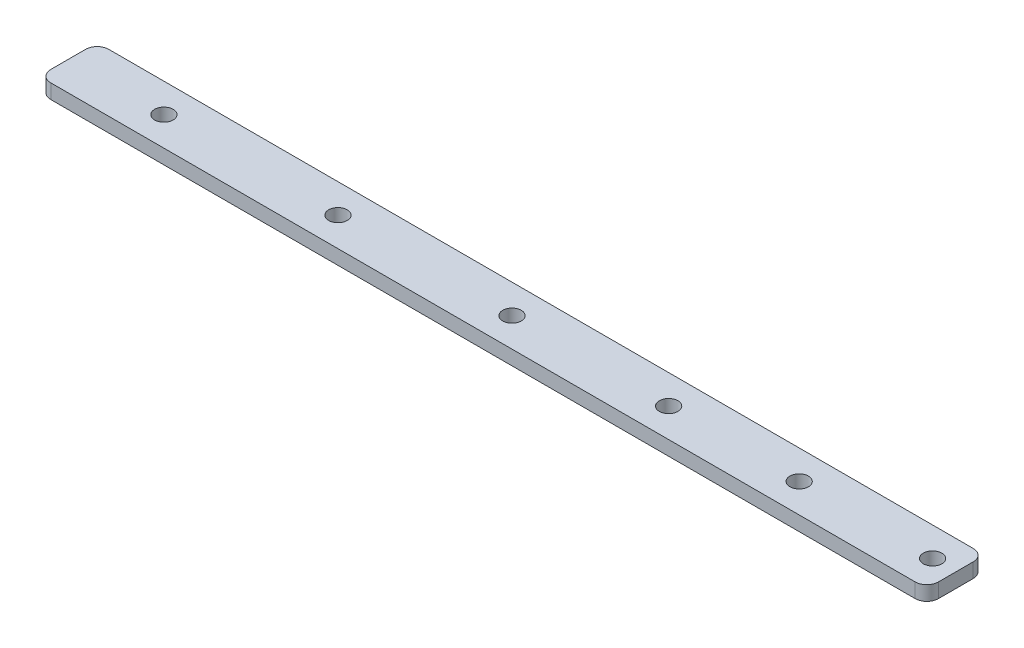
SolidWorks part; units mm, degrees
ref_plane "Front Plane" through (0, 0, 0) normal (0, 0, 1) x (1, 0, 0)
ref_plane "Top Plane" through (0, 0, 0) normal (0, 1, 0) x (1, 0, 0)
ref_plane "Right Plane" through (0, 0, 0) normal (1, 0, 0) x (0, 0, -1)
sketch "Sketch1" plane through (0, 0, 0) normal (0, 1, 0) x (1, 0, 0)
  line L1 (-97.155, -6.35) -> (97.155, -6.35)
  line L2 (-97.155, -6.35) -> (-97.155, 6.35)
  line L3 (-97.155, 6.35) -> (97.155, 6.35)
  line L4 (97.155, -6.35) -> (97.155, 6.35)
  line L5 (-97.155, -6.35) -> (97.155, 6.35) construction
  line L6 (-97.155, 6.35) -> (97.155, -6.35) construction
  point P0 (0, 0)
  dimension "D1" = 194.31
  dimension "D2" = 12.7
extrude "Boss-Extrude1" add sketch "Sketch1" along normal blind 3.175 contours L2 L3 L4 L1
fillet "Fillet1" radius 2.54 4 edges at (97.155, 1.5875, -6.35) (97.155, 1.5875, 6.35) (-97.155, 1.5875, 6.35) (-97.155, 1.5875, -6.35)
sketch "Sketch2" plane through (0, 3.175, 0) normal (0, 1, 0) x (1, 0, 0)
  line L0 (-97.155, 0) -> (97.155, 0) construction
  line L1 (-97.155, -3.81) -> (-97.155, 3.81) construction
  line L2 (97.155, -3.81) -> (97.155, 3.81) construction
  circle A0 centre (-76.2, 0) radius 2.032
  circle A1 centre (0, 0) radius 2.032
  circle A2 centre (-38.1, 0) radius 2.032
  circle A3 centre (92.075, 0) radius 2.032
  circle A4 centre (62.865, 0) radius 2.032
  circle A5 centre (34.29, 0) radius 2.032
  dimension "D1" = 4.064
  dimension "D2" = 5.08
  dimension "D3" = 34.29
  dimension "D4" = 38.1
  dimension "D5" = 76.2
  dimension "D6" = 34.29
extrude "Cut-Extrude1" cut sketch "Sketch2" against normal up to next
